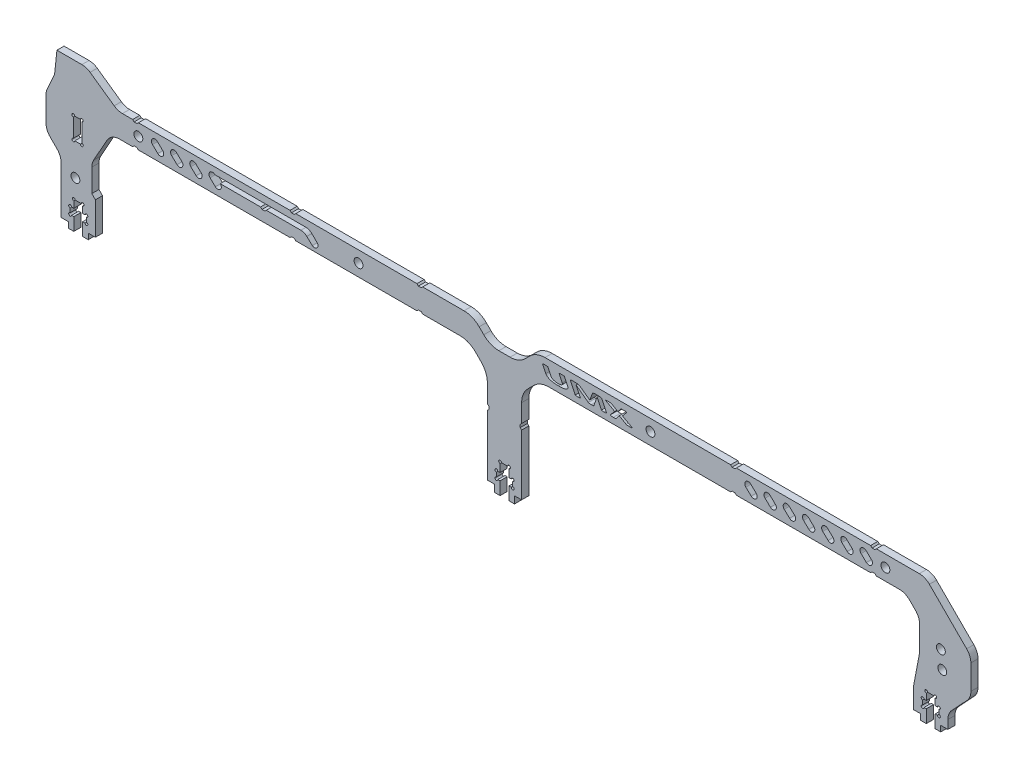
SolidWorks part; units mm, degrees
material "PPS"
ref_plane "前视基准面" through (0, 0, 0) normal (0, 0, 1) x (1, 0, 0)
ref_plane "上视基准面" through (0, 0, 0) normal (0, 1, 0) x (1, 0, 0)
ref_plane "右视基准面" through (0, 0, 0) normal (1, 0, 0) x (0, 0, -1)
sketch "草图1" plane through (0, 0, 0) normal (0, 0, 1) x (1, 0, 0)
  line L0 (-1000, 0) -> (49000, 0) construction
  line L1 (0, 0) -> (0, -218.3822) construction
  line L2 (6, -16.1697) -> (6, -48.75)
  line L3 (6, -48.75) -> (-6, -48.75) construction
  line L4 (-6, -16.1697) -> (-6, -48.75)
  line L5 (6, -48.75) -> (3.5, -48.75)
  line L6 (3.5, -48.75) -> (3.5, -51.25)
  line L7 (3.5, -51.25) -> (-3.5, -51.25) construction
  line L8 (-3.5, -48.75) -> (-3.5, -51.25)
  line L9 (-3.5, -48.75) -> (-6, -48.75)
  line L10 (1.55, -51.25) -> (1.55, -46.75)
  line L11 (1.55, -46.75) -> (2.85, -46.75)
  line L12 (2.85, -46.75) -> (2.85, -44.25)
  line L13 (2.85, -44.25) -> (1.55, -44.25)
  line L14 (1.55, -44.25) -> (1.55, -41)
  line L15 (1.55, -41) -> (-1.55, -41)
  line L16 (-1.55, -44.25) -> (-1.55, -41)
  line L17 (-2.85, -44.25) -> (-1.55, -44.25)
  line L18 (-2.85, -46.75) -> (-2.85, -44.25)
  line L19 (-1.55, -46.75) -> (-2.85, -46.75)
  line L20 (-1.55, -51.25) -> (-1.55, -46.75)
  line L21 (1.55, -51.25) -> (3.5, -51.25)
  line L22 (-1.55, -51.25) -> (-3.5, -51.25)
  line L23 (12.4197, -9.75) -> (6, -16.1697)
  line L24 (-12.4197, -9.75) -> (-6, -16.1697)
  line L25 (-147.7, -45.75) -> (-147.7, -41.25)
  line L26 (-150.8, -45.75) -> (-150.8, -41.25)
  line L27 (-147.7, -41.25) -> (-146.4, -41.25)
  line L28 (-146.4, -41.25) -> (-146.4, -38.75)
  line L29 (-146.4, -38.75) -> (-147.7, -38.75)
  line L30 (-147.7, -38.75) -> (-147.7, -36)
  line L31 (-150.8, -36) -> (-147.7, -36)
  line L32 (-150.8, -38.75) -> (-150.8, -36)
  line L33 (-152.1, -38.75) -> (-150.8, -38.75)
  line L34 (-152.1, -41.25) -> (-152.1, -38.75)
  line L35 (-150.8, -41.25) -> (-152.1, -41.25)
  line L36 (-5.0685, -7.5) -> (5.0685, -7.5)
  line L37 (5.0685, -7.5) -> (11.0685, -1.5)
  line L38 (11.0685, -1.5) -> (147.3211, -1.5)
  line L40 (145.3337, -25.5065) -> (145.3337, -14.709)
  line L41 (140.3747, -9.75) -> (12.4197, -9.75)
  line L42 (-5.0685, -7.5) -> (-11.0685, -1.5)
  line L44 (-11.0685, -1.5) -> (-157.5351, -1.5) construction
  line L45 (-137.7768, -9.75) -> (-12.4197, -9.75)
  line L50 (143.25, -36.4306) -> (143.25, -43.75)
  line L52 (155.25, -43.75) -> (143.25, -43.75) construction
  line L53 (155.25, -43.75) -> (152.75, -43.75)
  line L54 (152.75, -43.75) -> (152.75, -45.75)
  line L55 (152.75, -45.75) -> (145.75, -45.75) construction
  line L56 (145.75, -43.75) -> (145.75, -45.75)
  line L57 (145.75, -43.75) -> (143.25, -43.75)
  line L58 (150.8, -45.75) -> (150.8, -41.25)
  line L59 (150.8, -41.25) -> (152.1, -41.25)
  line L60 (152.1, -41.25) -> (152.1, -38.75)
  line L61 (152.1, -38.75) -> (150.8, -38.75)
  line L62 (150.8, -38.75) -> (150.8, -36)
  line L63 (150.8, -36) -> (147.7, -36)
  line L64 (147.7, -38.75) -> (147.7, -36)
  line L65 (146.4, -38.75) -> (147.7, -38.75)
  line L66 (146.4, -41.25) -> (146.4, -38.75)
  line L67 (147.7, -41.25) -> (146.4, -41.25)
  line L68 (147.7, -45.75) -> (147.7, -41.25)
  line L69 (150.8, -45.75) -> (152.75, -45.75)
  line L70 (147.7, -45.75) -> (145.75, -45.75)
  line L72 (57.6009, -1) -> (44.6221, -1) construction
  line L73 (145.3337, -25.5065) -> (143.25, -36.4306)
  line L74 (-147.7, -45.75) -> (-145.75, -45.75)
  line L75 (-150.8, -45.75) -> (-152.75, -45.75)
  line L76 (-152.75, -43.75) -> (-152.75, -45.75)
  line L77 (-155.25, -43.75) -> (-152.75, -43.75)
  line L78 (-145.75, -43.75) -> (-145.75, -45.75)
  line L79 (-145.75, -43.75) -> (-143.25, -43.75)
  line L80 (-157.5351, -1.5) -> (-160.547, -8.1912)
  line L81 (-160.547, -8.1912) -> (-160.547, -19.809)
  line L82 (-160.547, -19.809) -> (-155.25, -25.0873)
  line L87 (-143.25, -32.3726) -> (-144.5, -31.127)
  line L88 (-144.5, -31.127) -> (-144.5, -21.7902)
  line L89 (-144.5, -21.7902) -> (-137.7768, -9.75)
  line L90 (-155.25, -25.0873) -> (-155.25, -43.75)
  line L91 (-143.25, -32.3726) -> (-143.25, -43.75)
  line L92 (147.3211, -1.5) -> (163.2977, -17.4767)
  line L93 (163.2977, -17.4767) -> (163.2977, -30.1638)
  line L94 (163.2977, -30.1638) -> (155.25, -38.75)
  line L95 (155.25, -38.75) -> (155.25, -43.75)
  line L96 (-157.5351, -1.5) -> (-156.7241, 6.25)
  line L97 (-156.7241, 6.25) -> (-146.4, 6.25)
  line L98 (-146.4, 6.25) -> (-135.37, -1.5)
  line L99 (-135.37, -1.5) -> (-11.0685, -1.5)
  line L102 (140.3747, -9.75) -> (145.3337, -14.709)
  line L103 (56.6009, -9.75) -> (45.6221, -9.75) construction
  line L104 (146.1658, -18.25) -> (92.972, -18.25) construction
  line L105 (-154.7028, -11.25) -> (-130.7962, -11.25) construction
  circle A0 centre (-51.1115, -5.5) radius 1.55
  circle A1 centre (51.1115, -5.5) radius 1.55
  circle A5 centre (-51.1115, -5.5) radius 2.55 construction
  circle A6 centre (51.1115, -5.5) radius 2.55 construction
  point P6 (0, -48.75)
  point P11 (0, -51.25)
  point P20 (0, -41)
  point P29 (-149.25, -36)
  point P43 (152.75, -44.75)
  point P78 (149.25, -36)
  dimension "D21" = 3.1
  dimension "D1" = 3.5
  dimension "D2" = 4.5
  dimension "D3" = 2.5
  dimension "D4" = 6
  dimension "D5" = 135
  dimension "D6" = 2.5
  dimension "D7" = 48.75
  dimension "D8" = 25.5
  dimension "D9" = 2
  dimension "D10" = 7
  dimension "D11" = 149.25
  dimension "D12" = 1.95
  dimension "D13" = 1.55
  dimension "D14" = 2.85
  dimension "D15" = 10.25
  dimension "D16" = 0.5
  dimension "D17" = 2.25
  dimension "D18" = 135
  dimension "D19" = 135
  dimension "D20" = 1.25
  dimension "D22" = 17.5
extrude "凸台-拉伸1" add sketch "草图1" along normal blind 2.5
sketch "草图2" plane through (0, 0, 0) normal (0, 0, 1) x (1, 0, 0)
  line L0 (98.8244, -4.7341) -> (98.8244, -1.5) construction
  line L2 (147.3211, -1.5) -> (11.0685, -1.5) construction
  line L4 (100.6889, -6.5159) -> (100.6889, -9.75) construction
  line L7 (12.4197, -9.75) -> (140.3747, -9.75) construction
  line L8 (94.8107, -5.6378) -> (97.9607, -5.6378) construction
  line L11 (86.3905, -7.4197) -> (84.526, -5.6378)
  line L16 (121.7047, -5.6122) -> (124.8547, -5.6122) construction
  line L17 (106.5671, -7.394) -> (104.7026, -5.6122)
  line L18 (104.7026, -5.6122) -> (106.4054, -3.8303) construction
  line L19 (106.4054, -3.8303) -> (108.27, -5.6122)
  line L20 (108.27, -5.6122) -> (106.5671, -7.394) construction
  line L21 (99.8252, -7.4197) -> (97.9607, -5.6378)
  line L22 (99.6881, -3.8303) -> (101.5526, -5.6122)
  line L23 (101.5526, -5.6122) -> (104.7026, -5.6122) construction
  line L24 (108.27, -5.6122) -> (111.42, -5.6122) construction
  line L25 (113.2845, -7.394) -> (111.42, -5.6122)
  line L26 (113.1228, -3.8303) -> (114.9873, -5.6122)
  line L27 (114.9873, -5.6122) -> (118.1373, -5.6122) construction
  line L28 (120.0018, -7.394) -> (118.1373, -5.6122)
  line L29 (119.8402, -3.8303) -> (121.7047, -5.6122)
  line L30 (126.7192, -7.394) -> (124.8547, -5.6122)
  line L31 (126.5819, -3.8048) -> (128.4464, -5.5866)
  line L32 (86.2289, -3.856) -> (88.0934, -5.6378)
  line L33 (88.0934, -5.6378) -> (91.2434, -5.6378) construction
  line L34 (93.1079, -7.4197) -> (91.2434, -5.6378)
  line L35 (92.9462, -3.856) -> (94.8107, -5.6378)
  line L36 (-106.2679, -5.6378) -> (-103.1179, -5.6378) construction
  line L38 (-112.9852, -5.6378) -> (-109.8352, -5.6378) construction
  line L39 (-121.4054, -7.4197) -> (-123.27, -5.6378)
  line L42 (-107.9707, -7.4197) -> (-109.8352, -5.6378)
  line L44 (-108.1324, -3.856) -> (-106.2679, -5.6378)
  line L47 (-101.2387, -7.4197) -> (-103.1032, -5.6378)
  line L48 (-101.4003, -3.856) -> (-99.5358, -5.6378) construction
  line L51 (-101.4003, -3.856) -> (-69.6149, -3.856)
  line L56 (-121.5671, -3.856) -> (-119.7026, -5.6378)
  line L57 (-119.7026, -5.6378) -> (-116.5526, -5.6378) construction
  line L58 (-114.6881, -7.4197) -> (-116.5526, -5.6378)
  line L59 (-114.8498, -3.856) -> (-112.9852, -5.6378)
  line L60 (-71.3031, -5.6378) -> (-99.5358, -5.6378)
  line L66 (-67.5422, -4.6871) -> (-65.6228, -6.5214)
  line L69 (-67.311, -8.3033) -> (-69.2304, -6.469)
  arc A10 (126.5819, -3.8048) -> (124.8547, -5.6122) centre (125.7183, -4.7085) ccw
  arc A11 (128.4464, -5.5866) -> (126.7192, -7.394) centre (127.5828, -6.4903) cw
  arc A12 (106.4054, -3.8303) -> (104.7026, -5.6122) centre (105.554, -4.7213) ccw
  arc A13 (108.27, -5.6122) -> (106.5671, -7.394) centre (107.4185, -6.5031) cw
  arc A14 (99.6881, -3.8303) -> (97.9607, -5.6378) centre (98.8244, -4.7341) ccw
  arc A15 (101.5526, -5.6122) -> (99.8252, -7.4197) centre (100.6889, -6.5159) cw
  arc A16 (113.1228, -3.8303) -> (111.42, -5.6122) centre (112.2714, -4.7213) ccw
  arc A17 (114.9873, -5.6122) -> (113.2845, -7.394) centre (114.1359, -6.5031) cw
  arc A18 (119.8402, -3.8303) -> (118.1373, -5.6122) centre (118.9887, -4.7213) ccw
  arc A19 (121.7047, -5.6122) -> (120.0018, -7.394) centre (120.8532, -6.5031) cw
  arc A20 (86.2289, -3.856) -> (84.526, -5.6378) centre (85.3774, -4.7469) ccw
  arc A21 (88.0934, -5.6378) -> (86.3905, -7.4197) centre (87.242, -6.5287) cw
  arc A22 (92.9462, -3.856) -> (91.2434, -5.6378) centre (92.0948, -4.7469) ccw
  arc A23 (94.8107, -5.6378) -> (93.1079, -7.4197) centre (93.9593, -6.5287) cw
  arc A34 (-121.5671, -3.856) -> (-123.27, -5.6378) centre (-122.4185, -4.7469) ccw
  arc A35 (-119.7026, -5.6378) -> (-121.4054, -7.4197) centre (-120.554, -6.5287) cw
  arc A36 (-114.8498, -3.856) -> (-116.5526, -5.6378) centre (-115.7012, -4.7469) ccw
  arc A37 (-112.9852, -5.6378) -> (-114.6881, -7.4197) centre (-113.8367, -6.5287) cw
  arc A38 (-108.1324, -3.856) -> (-109.8352, -5.6378) centre (-108.9838, -4.7469) ccw
  arc A39 (-106.2679, -5.6378) -> (-107.9707, -7.4197) centre (-107.1193, -6.5287) cw
  arc A40 (-101.4003, -3.856) -> (-103.1032, -5.6378) centre (-102.2518, -4.7469) ccw
  arc A41 (-99.5358, -5.6378) -> (-101.2387, -7.4197) centre (-100.3873, -6.5287) cw
  arc A46 (-71.3031, -5.6378) -> (-69.2304, -6.469) centre (-71.3031, -8.6378) cw
  arc A47 (-65.6228, -6.5214) -> (-67.311, -8.3033) centre (-66.548, -7.3355) cw
  arc A48 (-69.6149, -3.856) -> (-67.5422, -4.6871) centre (-69.6149, -6.856) cw
extrude "减重" cut sketch "草图2" against normal through all from surface starting at face at (-5.419, -33.6883, 2.5)
sketch "草图5" plane through (0, 0, 0) normal (0, 0, 1) x (1, 0, 0)
  line L0 (-123.27, -5.6378) -> (-121.4054, -7.4197) construction
  line L1 (-126.42, -5.6378) -> (-123.27, -5.6378) construction
  line L2 (-126.42, -5.6378) -> (-128.2845, -3.856) construction
  line L3 (-128.1228, -7.4197) -> (-129.9873, -5.6378) construction
  line L4 (-129.1359, -4.7469) -> (-127.2714, -6.5287) construction
  line L5 (132.4479, -4.6957) -> (134.3124, -6.4776) construction
  line L9 (128.4464, -5.5866) -> (131.5964, -5.5866) construction
  line L10 (135.1638, -5.5866) -> (133.2993, -3.8048) construction
  line L11 (133.4609, -7.3685) -> (131.5964, -5.5866) construction
  arc A1 (-126.42, -5.6378) -> (-128.1228, -7.4197) centre (-127.2714, -6.5287) cw construction
  arc A2 (-129.9873, -5.6378) -> (-128.2845, -3.856) centre (-129.1359, -4.7469) cw construction
  arc A7 (135.1638, -5.5866) -> (133.4609, -7.3685) centre (134.3124, -6.4776) cw construction
  arc A8 (131.5964, -5.5866) -> (133.2993, -3.8048) centre (132.4479, -4.6957) cw construction
  circle A9 centre (-128.2036, -5.6378) radius 1.55
  circle A11 centre (133.3801, -5.5866) radius 1.55
  dimension "D1" = 3.1
extrude "光球接口" cut sketch "草图5" along normal through all
sketch "草图3" plane through (0, 0, 2.5) normal (0, 0, 1) x (1, 0, 0)
  text T0 "<b><i>XMU</i></b>" font "Calibri" height 3.95
extrude "切除-拉伸3" cut sketch "草图3" against normal through all
sketch "草图4" plane through (0, 0, 0) normal (0, 0, 1) x (1, 0, 0)
  line L0 (-6, -25.591) -> (-5.5, -26.091)
  line L1 (-6, -16.1697) -> (-6, -48.75) construction
  line L2 (-5.5, -26.091) -> (-5.5, -27.091)
  line L3 (-5.5, -27.091) -> (-6, -27.591)
  line L4 (-6, -27.591) -> (-6, -25.591)
  line L5 (0, 0) -> (0, -67.6388) construction
  line L6 (6, -27.591) -> (6, -25.591)
  line L7 (5.5, -27.091) -> (6, -27.591)
  line L8 (5.5, -26.091) -> (5.5, -27.091)
  line L9 (6, -25.591) -> (5.5, -26.091)
  line L18 (-11.0685, -1.5) -> (-135.37, -1.5) construction
  line L19 (-128.2051, -1.5) -> (-130.2051, -1.5)
  line L20 (-128.7051, -2) -> (-128.2051, -1.5)
  line L21 (-129.7051, -2) -> (-128.7051, -2)
  line L22 (-130.2051, -1.5) -> (-129.7051, -2)
  line L23 (0, 0) -> (-134.5835, 0) construction
  line L36 (-137.7768, -9.75) -> (-12.4197, -9.75) construction
  line L41 (-99.5358, -5.6378) -> (-71.3031, -5.6378) construction
  line L46 (130.2051, -1.5) -> (129.7051, -2)
  line L47 (129.7051, -2) -> (128.7051, -2)
  line L48 (128.7051, -2) -> (128.2051, -1.5)
  line L49 (128.2051, -1.5) -> (130.2051, -1.5)
  line L50 (-135.37, -1.5) -> (-135.37, -9.75) construction
  line L51 (-1135.37, -5.625) -> (48864.63, -5.625) construction
  line L52 (-130.2051, -9.75) -> (-129.7051, -9.25)
  line L53 (-129.7051, -9.25) -> (-128.7051, -9.25)
  line L54 (-128.7051, -9.25) -> (-128.2051, -9.75)
  line L55 (-128.2051, -9.75) -> (-130.2051, -9.75)
  line L64 (-73.0982, -1.5) -> (-75.0982, -1.5)
  line L65 (-73.5982, -2) -> (-73.0982, -1.5)
  line L66 (-74.5982, -2) -> (-73.5982, -2)
  line L67 (-75.0982, -1.5) -> (-74.5982, -2)
  line L68 (-75.0982, -9.75) -> (-74.5982, -9.25)
  line L69 (-74.5982, -9.25) -> (-73.5982, -9.25)
  line L70 (-73.5982, -9.25) -> (-73.0982, -9.75)
  line L71 (-73.0982, -9.75) -> (-75.0982, -9.75)
  line L72 (-28.6523, -1.5) -> (-30.6523, -1.5)
  line L73 (-29.1523, -2) -> (-28.6523, -1.5)
  line L74 (-30.1523, -2) -> (-29.1523, -2)
  line L75 (-30.6523, -1.5) -> (-30.1523, -2)
  line L76 (-30.6523, -9.75) -> (-30.1523, -9.25)
  line L77 (-30.1523, -9.25) -> (-29.1523, -9.25)
  line L78 (-29.1523, -9.25) -> (-28.6523, -9.75)
  line L79 (-28.6523, -9.75) -> (-30.6523, -9.75)
  line L80 (-83.4194, -5.6378) -> (-85.4194, -5.6378)
  line L81 (-83.9194, -6.1378) -> (-83.4194, -5.6378)
  line L82 (-84.9194, -6.1378) -> (-83.9194, -6.1378)
  line L83 (-85.4194, -5.6378) -> (-84.9194, -6.1378)
  line L92 (79.1823, -9.75) -> (81.1823, -9.75)
  line L93 (128.2051, -9.75) -> (130.2051, -9.75)
  line L94 (128.7051, -9.25) -> (128.2051, -9.75)
  line L95 (129.7051, -9.25) -> (128.7051, -9.25)
  line L96 (130.2051, -9.75) -> (129.7051, -9.25)
  line L97 (-151, -10.625) -> (-148, -10.625)
  line L98 (-148, -10.625) -> (-148, -18.125)
  line L99 (-148, -18.125) -> (-151, -18.125)
  line L100 (-151, -18.125) -> (-151, -10.625)
  line L101 (79.6823, -9.25) -> (79.1823, -9.75)
  line L102 (80.6823, -9.25) -> (79.6823, -9.25)
  line L103 (81.1823, -9.75) -> (80.6823, -9.25)
  line L104 (81.1823, -1.5) -> (80.6823, -2)
  line L105 (80.6823, -2) -> (79.6823, -2)
  line L106 (79.6823, -2) -> (79.1948, -1.5)
  line L107 (79.1948, -1.5) -> (81.1823, -1.5)
  line L108 (147.3211, -1.5) -> (11.0685, -1.5) construction
  line L109 (163.2977, -30.1638) -> (163.2977, -17.4767) construction
  line L110 (-144.5, -31.127) -> (-144.5, -21.7902) construction
  line L112 (-155.25, -43.75) -> (-152.75, -43.75) construction
  circle A0 centre (-150.25, -29.25) radius 1.55
  circle A1 centre (152.7976, -20.675) radius 1.55
  circle A2 centre (153.2976, -26.6541) radius 1.55
  point P4 (-6, -26.591)
  point P19 (-85.4194, -5.6378)
  point P49 (-135.37, -5.625)
  dimension "D13" = 3.1
  dimension "D20" = 3.1
  dimension "D1" = 45
  dimension "D2" = 0.5
  dimension "D3" = 1
  dimension "D4" = 45
  dimension "D5" = 0.5
  dimension "D6" = 1
  dimension "D7" = 45
  dimension "D8" = 1
  dimension "D9" = 6
  dimension "D10" = 15.05
  dimension "D11" = 10.0002
  dimension "D12" = 0.5
  dimension "D14" = 5
  dimension "D15" = 7.5
  dimension "D16" = 3
  dimension "D17" = 14.5
  dimension "D18" = 3.5
  dimension "D19" = 5.75
extrude "线槽和设备接口" cut sketch "草图4" along normal through all
fillet "圆角2" radius 5 16 edges at (155.25, -38.75, 1.25) (145.3337, -25.5065, 1.25) (143.25, -36.4306, 1.25) (147.3211, -1.5, 1.25) (163.2977, -30.1638, 1.25) (163.2977, -17.4767, 1.25) (145.3337, -14.709, 1.25) (140.3747, -9.75, 1.25) (-137.7768, -9.75, 1.25) (-144.5, -21.7902, 1.25) (-146.4, 6.25, 1.25) (-155.25, -25.0873, 1.25) (-160.547, -19.809, 1.25) (-160.547, -8.1912, 1.25) (-157.5351, -1.5, 1.25) (-135.37, -1.5, 1.25)
fillet "圆角3" radius 7.5 8 edges at (12.4197, -9.75, 1.25) (6, -16.1697, 1.25) (-6, -16.1697, 1.25) (-12.4197, -9.75, 1.25) (11.0685, -1.5, 1.25) (5.0685, -7.5, 1.25) (-5.0685, -7.5, 1.25) (-11.0685, -1.5, 1.25)
sketch "草图6" plane through (0, 0, 2.5) normal (0, 0, 1) x (1, 0, 0)
  line L0 (0, 0) -> (0, -63.5679) construction
  circle A0 centre (-151, -10.625) radius 0.5
  circle A1 centre (-148, -10.625) radius 0.5
  circle A2 centre (-151, -18.125) radius 0.5
  circle A3 centre (-148, -18.125) radius 0.5
  circle A4 centre (-150.8, -36) radius 0.5
  circle A5 centre (-147.7, -36) radius 0.5
  circle A6 centre (-152.1, -38.75) radius 0.5
  circle A7 centre (-152.1, -41.25) radius 0.5
  circle A8 centre (-146.4, -38.75) radius 0.5
  circle A9 centre (-146.4, -41.25) radius 0.5
  circle A10 centre (-2.85, -44.25) radius 0.5
  circle A11 centre (-2.85, -46.75) radius 0.5
  circle A12 centre (-1.55, -41) radius 0.5
  circle A13 centre (-3.5, -48.75) radius 0.5 construction
  circle A15 centre (-152.75, -43.75) radius 0.5 construction
  circle A16 centre (-145.75, -43.75) radius 0.5 construction
  circle A17 centre (145.75, -43.75) radius 0.5 construction
  circle A18 centre (152.75, -43.75) radius 0.5 construction
  circle A19 centre (3.5, -48.75) radius 0.5 construction
  circle A20 centre (1.55, -41) radius 0.5
  circle A21 centre (2.85, -46.75) radius 0.5
  circle A22 centre (2.85, -44.25) radius 0.5
  circle A23 centre (146.4, -41.25) radius 0.5
  circle A24 centre (146.4, -38.75) radius 0.5
  circle A25 centre (152.1, -41.25) radius 0.5
  circle A26 centre (152.1, -38.75) radius 0.5
  circle A27 centre (147.7, -36) radius 0.5
  circle A28 centre (150.8, -36) radius 0.5
  dimension "D1" = 1
extrude "直角约束" cut sketch "草图6" against normal through all
